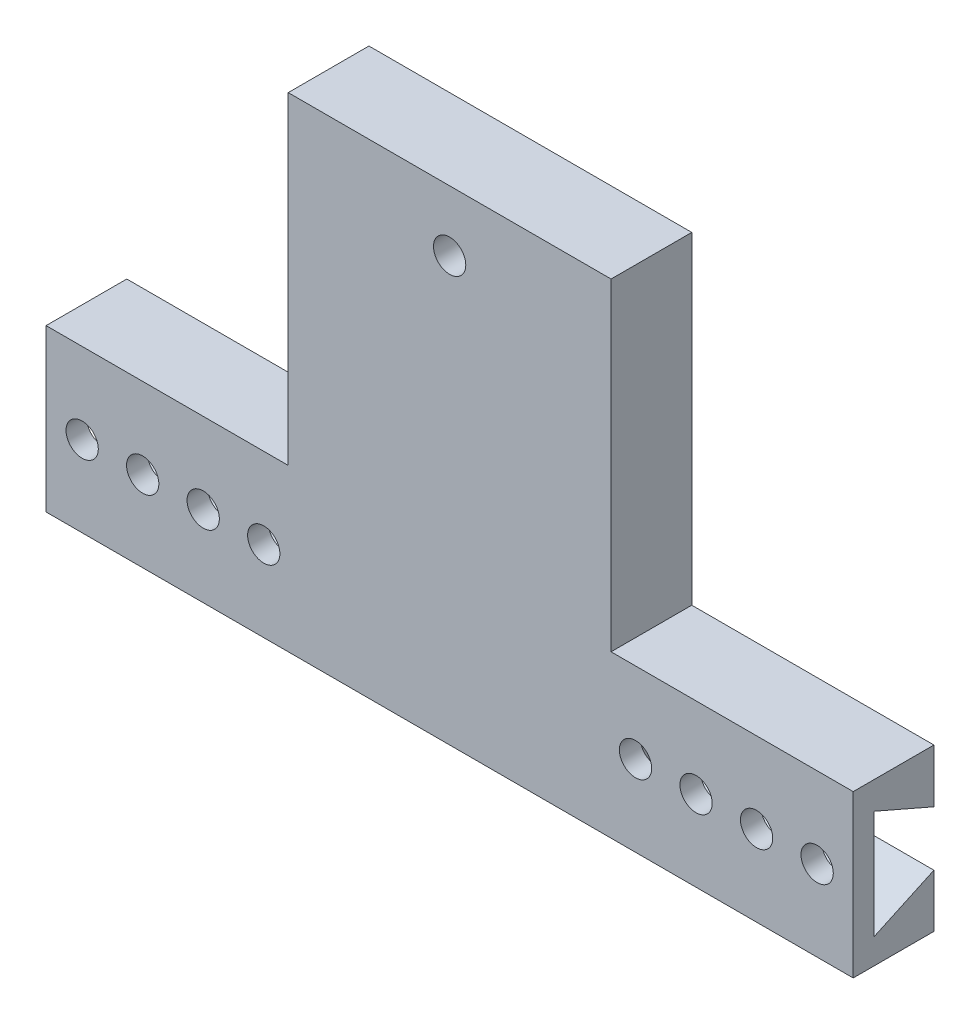
SolidWorks part; units mm, degrees
ref_plane "Front Plane" through (0, 0, 0) normal (0, 0, 1) x (1, 0, 0)
ref_plane "Top Plane" through (0, 0, 0) normal (0, 1, 0) x (1, 0, 0)
ref_plane "Right Plane" through (0, 0, 0) normal (1, 0, 0) x (0, 0, -1)
sketch "Sketch1" plane through (0, 0, 0) normal (0, 1, 0) x (1, 0, 0)
  line L1 (-20, 5) -> (20, 5)
  line L2 (-20, 5) -> (-20, -5)
  line L3 (-20, -5) -> (20, -5)
  line L4 (20, 5) -> (20, -5)
  line L5 (-20, 5) -> (20, -5) construction
  line L6 (-20, -5) -> (20, 5) construction
  point P0 (0, 0)
extrude "Boss-Extrude1" add sketch "Sketch1" against normal blind 60
sketch "Sketch2" plane through (20, 0, 0) normal (1, 0, 0) x (0, 0, -1)
  line L0 (-5, -60) -> (-5, 0) construction
  line L1 (5, -60) -> (-5, -60)
  line L2 (5, -60) -> (5, -40)
  line L3 (5, -40) -> (-5, -40)
  line L4 (-5, -60) -> (-5, -40)
  line L5 (0, -40) -> (0, -60) construction
  line L6 (5, -50) -> (-5, -50) construction
  point P532 (0, -50)
extrude "Boss-Extrude2" add sketch "Sketch2" along normal blind 30 contours L3 L4 L1 L2
sketch "Sketch3" plane through (50, 0, 0) normal (1, 0, 0) x (0, 0, -1)
  line L0 (-2.4245, -50.3998) -> (-2.4245, -56.8645)
  line L1 (-2.4245, -56.8645) -> (5, -53.4322)
  line L2 (5, -60) -> (5, -40) construction
  line L3 (-2.4245, -50.3998) -> (-2.4245, -43.3998)
  line L4 (-2.4245, -43.3998) -> (5, -46.6321)
  line L5 (5, -53.4322) -> (5, -46.6321)
extrude "Cut-Extrude1" cut sketch "Sketch3" against normal blind 30 contours L0 L1 L5 L4 L3
sketch "Sketch6" plane through (0, 0, 5) normal (0, 0, 1) x (1, 0, 0)
  line L0 (50, -40) -> (20, -40) construction
  circle A0 centre (45.5304, -50) radius 2
  dimension "D1" = 10
extrude "Cut-Extrude2" cut sketch "Sketch6" against normal through all contours A0
pattern_linear "LPattern1" count 4 spacing 7.5 along (-1, 0, 0) of "Cut-Extrude2"
mirror "Mirror3" about plane through (0, 0, 0) normal (1, 0, 0) of "LPattern1", "Cut-Extrude1", "Boss-Extrude2"
sketch "Sketch7" plane through (0, 0, 5) normal (0, 0, 1) x (1, 0, 0)
  circle A0 centre (0, -7.5) radius 2
  dimension "D1" = 7.5
extrude "Cut-Extrude3" cut sketch "Sketch7" against normal blind 30
